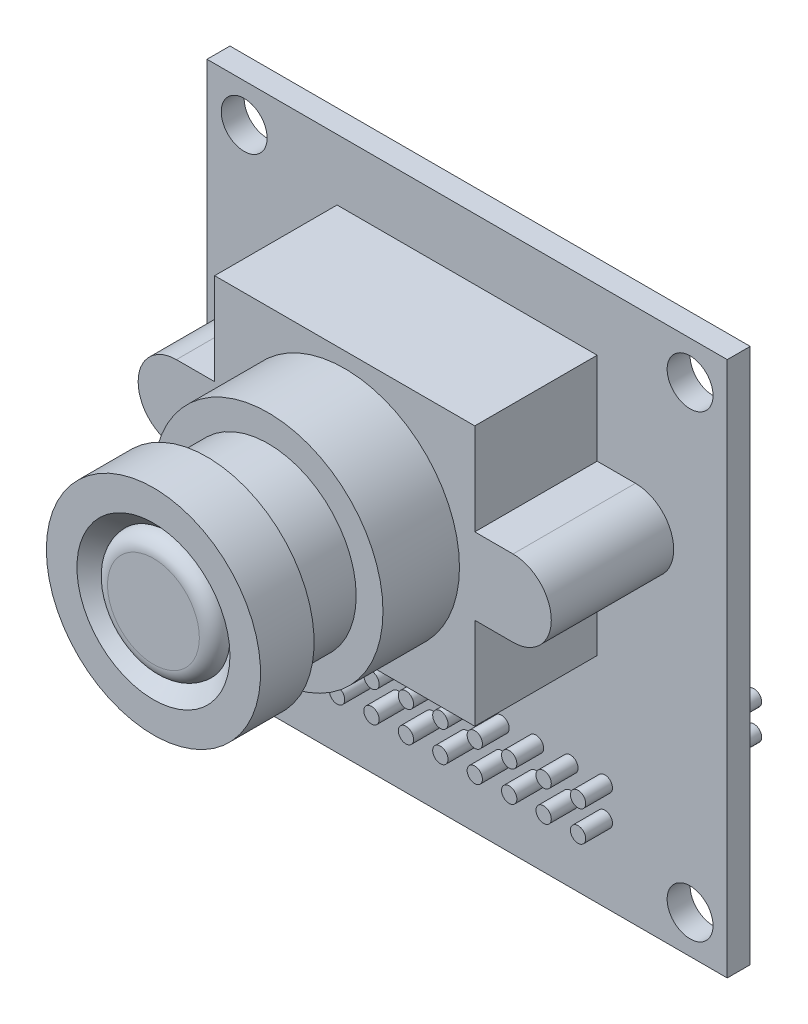
SolidWorks part; units mm, degrees
material "PVC Rígido"
ref_plane "Alzado" through (0, 0, 0) normal (0, 0, 1) x (1, 0, 0)
ref_plane "Planta" through (0, 0, 0) normal (0, 1, 0) x (1, 0, 0)
ref_plane "Vista lateral" through (0, 0, 0) normal (1, 0, 0) x (0, 0, -1)
sketch "Croquis1" plane through (0, 0, 0) normal (0, 0, 1) x (1, 0, 0)
  line L0 (0, 17.5) -> (0, -17.5) construction
  line L1 (-17, 17.5) -> (17, 17.5)
  line L2 (-17, 17.5) -> (-17, -17.5)
  line L3 (-17, -17.5) -> (17, -17.5)
  line L4 (17, 17.5) -> (17, -17.5)
  line L5 (-17, 17.5) -> (17, -17.5) construction
  line L6 (-17, -17.5) -> (17, 17.5) construction
  line L7 (-17, 0) -> (17, 0) construction
  circle A0 centre (-14.5714, 15) radius 1.5
  circle A1 centre (14.5714, 15) radius 1.5
  circle A2 centre (14.5714, -15) radius 1.5
  circle A3 centre (-14.5714, -15) radius 1.5
  point P0 (0, 0)
  dimension "D3" = 3
  dimension "D4" = 2.5
  dimension "D1" = 35
  dimension "D2" = 34
extrude "Saliente-Extruir1" add sketch "Croquis1" along normal blind 1.5
sketch "Croquis2" plane through (0, 0, 0) normal (0, 0, -1) x (-1, 0, 0)
  line L0 (0, 0) -> (0, -17.5) construction
  line L1 (11.25, -14) -> (-11.25, -14)
  line L2 (11.25, -14) -> (11.25, -9)
  line L3 (11.25, -9) -> (-11.25, -9)
  line L4 (-11.25, -14) -> (-11.25, -9)
  line L5 (11.25, -14) -> (-11.25, -9) construction
  line L6 (11.25, -9) -> (-11.25, -14) construction
  line L7 (17, -17.5) -> (-17, -17.5) construction
  point P0 (0, -11.5)
  point P10 (0, 0)
  dimension "D1" = 5
  dimension "D2" = 22.5
  dimension "D3" = 3.5
extrude "Saliente-Extruir2" add sketch "Croquis2" along normal blind 2.5
sketch "Croquis3" plane through (0, 0, 1.5) normal (0, 0, 1) x (1, 0, 0)
  line L0 (0, 17.5) -> (0, -17.5) construction
  line L1 (17, 17.5) -> (-17, 17.5) construction
  line L2 (-17, -17.5) -> (17, -17.5) construction
  line L3 (-8.5, 5) -> (8.5, 5) construction
  line L4 (-8.5, 13.5) -> (8.5, 13.5)
  line L5 (-8.5, 13.5) -> (-8.5, 7.5)
  line L6 (-8.5, -3.5) -> (8.5, -3.5)
  line L7 (8.5, 13.5) -> (8.5, 7.5)
  line L8 (-8.5, 13.5) -> (8.5, -3.5) construction
  line L9 (-8.5, -3.5) -> (8.5, 13.5) construction
  line L10 (-11, 7.5) -> (-8.5, 7.5)
  line L11 (-11, 2.5) -> (-8.5, 2.5)
  line L12 (-8.5, 2.5) -> (-8.5, -3.5)
  line L13 (11, 2.5) -> (8.5, 2.5)
  line L14 (11, 7.5) -> (8.5, 7.5)
  line L15 (8.5, 2.5) -> (8.5, -3.5)
  arc A0 (-11, 7.5) -> (-11, 2.5) centre (-11, 5) ccw
  arc A1 (11, 7.5) -> (11, 2.5) centre (11, 5) cw
  point P6 (0, 5)
  dimension "D3" = 5
  dimension "D1" = 17
  dimension "D2" = 4
extrude "Saliente-Extruir3" add sketch "Croquis3" along normal blind 8
sketch "Croquis4" plane through (0, 0, 9.5) normal (0, 0, 1) x (1, 0, 0)
  circle A0 centre (0, 5) radius 7.5
  dimension "D1" = 15
extrude "Saliente-Extruir4" add sketch "Croquis4" along normal blind 5
sketch "Croquis5" plane through (0, 0, 14.5) normal (0, 0, 1) x (1, 0, 0)
  circle A0 centre (0, 5) radius 5.75
  dimension "D1" = 11.5
extrude "Saliente-Extruir5" add sketch "Croquis5" along normal blind 4
sketch "Croquis6" plane through (0, 0, 18.5) normal (0, 0, 1) x (1, 0, 0)
  circle A0 centre (0, 5) radius 7
  dimension "D1" = 14
extrude "Saliente-Extruir6" add sketch "Croquis6" along normal blind 3.5
sketch "Croquis7" plane through (0, 0, 22) normal (0, 0, 1) x (1, 0, 0)
  circle A0 centre (0, 5) radius 5
  dimension "D1" = 10
extrude "Cortar-Extruir1" cut sketch "Croquis7" against normal blind 1 draft 45
sketch "Croquis8" plane through (0, 0, 21) normal (0, 0, 1) x (1, 0, 0)
  circle A0 centre (0, 5) radius 4
  dimension "D1" = 8
extrude "Saliente-Extruir7" add sketch "Croquis8" along normal blind 1
fillet "Redondeo1" radius 1 1 edges at (4, 5, 22)
sketch "Croquis10" plane through (0, 0, -2.5) normal (0, 0, -1) x (-1, 0, 0)
  line L1 (-11.25, -14) -> (11.25, -14) construction
  line L2 (-11.25, -9) -> (-11.25, -14) construction
  circle A0 centre (-9, -12.5) radius 0.5
  circle A1 centre (-9, -10.5) radius 0.5
  circle A2 centre (-6.75, -10.5) radius 0.5
  circle A3 centre (-4.5, -10.5) radius 0.5
  circle A4 centre (-2.25, -10.5) radius 0.5
  circle A5 centre (0, -10.5) radius 0.5
  circle A6 centre (2.25, -10.5) radius 0.5
  circle A7 centre (4.5, -10.5) radius 0.5
  circle A8 centre (6.75, -10.5) radius 0.5
  circle A9 centre (9, -10.5) radius 0.5
  circle A10 centre (-6.75, -12.5) radius 0.5
  circle A11 centre (-4.5, -12.5) radius 0.5
  circle A12 centre (-2.25, -12.5) radius 0.5
  circle A13 centre (0, -12.5) radius 0.5
  circle A14 centre (2.25, -12.5) radius 0.5
  circle A15 centre (4.5, -12.5) radius 0.5
  circle A16 centre (6.75, -12.5) radius 0.5
  circle A17 centre (9, -12.5) radius 0.5
  dimension "D1" = 1
  dimension "D2" = 1.5
  dimension "D3" = 2.25
  dimension "D4" = 2
  dimension "D5" = 9
  dimension "D6" = 9
extrude "Saliente-Extruir8" add sketch "Croquis10" along normal mid plane 11.5
